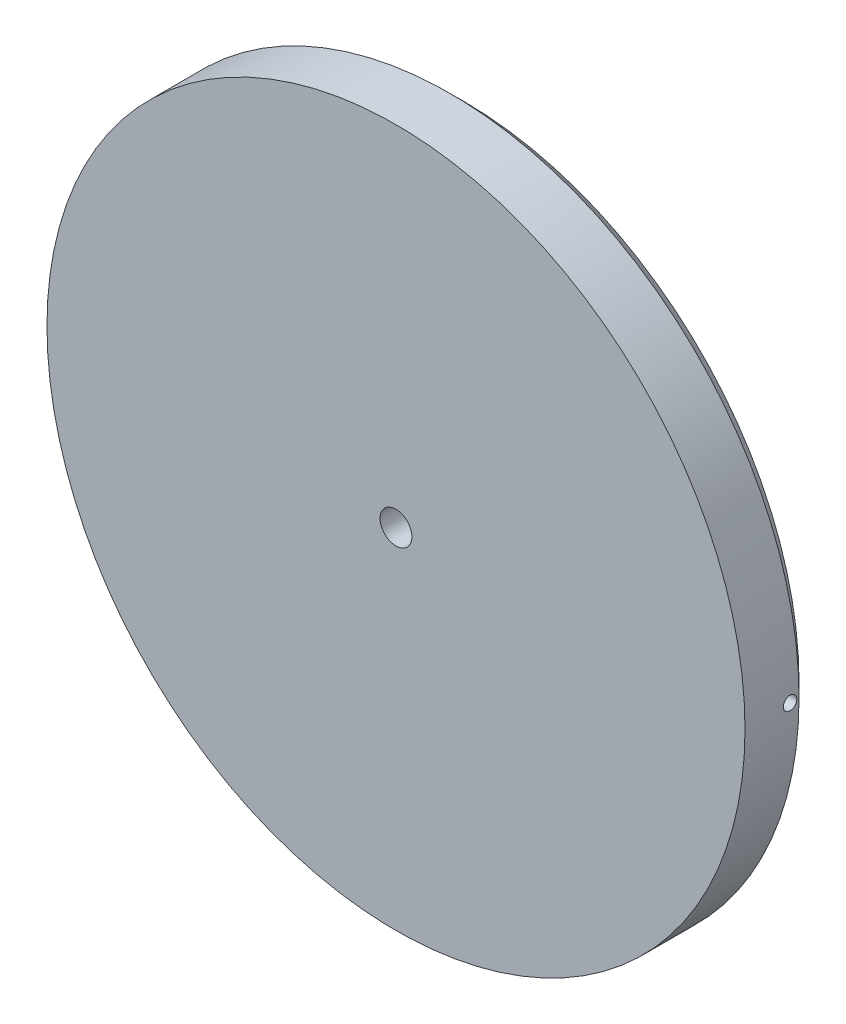
SolidWorks part; units mm, degrees
ref_plane "Front Plane" through (0, 0, 0) normal (0, 0, 1) x (1, 0, 0)
ref_plane "Top Plane" through (0, 0, 0) normal (0, 1, 0) x (1, 0, 0)
ref_plane "Right Plane" through (0, 0, 0) normal (1, 0, 0) x (0, 0, -1)
ref_axis "Z" through (0, 0, 543.0939) along (0, 0, -1)
ref_axis "X" through (17.0818, 0, 0) along (-1, 0, 0)
ref_axis "Y" through (0, 20.242, 0) along (0, -1, 0)
sketch "Sketch1" plane through (0, 0, 0) normal (0, 0, 1) x (1, 0, 0)
  circle A0 centre (0, 0) radius 77.5
  circle A1 centre (0, 0) radius 3.535
  dimension "D1" = 155
  dimension "D2" = 7.07
extrude "Boss-Extrude1" add sketch "Sketch1" against normal blind 5 and the other way blind 10
sketch "Sketch2" plane through (0, 0, 0) normal (0, 1, 0) x (1, 0, 0)
  line L0 (-16.3173, 0) -> (16.3173, 0) construction
  line L1 (0, -20.5521) -> (0, 20.5521) construction
  circle A0 centre (0, 0) radius 1.5
  dimension "D1" = 3
extrude "Cut-Extrude1" cut sketch "Sketch2" against normal through all
sketch "Sketch3" plane through (0, 0, 0) normal (1, 0, 0) x (0, 0, -1)
  circle A0 centre (0, 0) radius 1.5
  dimension "D1" = 3
extrude "Cut-Extrude2" cut sketch "Sketch3" along normal through all
chamfer "Chamfer1" distance 3 angle 45 1 edges at (77.5, 0, -5)
sketch "Sketch4" plane through (0, 0, 0) normal (0, 0, 1) x (1, 0, 0)
  circle A0 centre (0, 0) radius 3.535
  circle A2 centre (0, 0) radius 3.535 construction
  circle A3 centre (0, 0) radius 71.5
  dimension "D1" = 143
extrude "Boss-Extrude2" add sketch "Sketch4" along normal up to surface and the other way up to surface up to face at (77.5, 0, 10) other way up to face at (74.5, 0, -5)
sketch "Sketch5" plane through (0, 0, 0) normal (0, 0, 1) x (1, 0, 0)
  line L0 (0, 0) -> (0, -94.5) construction
  dimension "D1" = 94.5
ref_plane "Vert" through (0, 0, 0) normal (0.7071, 0.7071, 0) x (0, 0, -1)
equation "\"EyeDiameter\" = 155"
equation "\"BasePlaneDistance\" = \"EyeDiameter\"/2+\"L2Thickness\"+\"EyeClearance\""
equation "\"EyeClearance\" = 2"
equation "\"EyeOD\"= \"EyeDiameter\""
equation "\"D1@Sketch1\"=\"EyeOD\""
equation "\"D2@Sketch1\"= 7.07"
equation "\"pinHoleDiameter\"= 3"
equation "\"D1@Sketch2\"=\"pinHoleDiameter\""
equation "\"D1@Sketch3\"=\"pinHoleDiameter\""
equation "\"D1@Sketch4\"=\"EyeDiameter\"-12"
equation "\"D1@Sketch5\"=\"BasePlaneDistance\""
